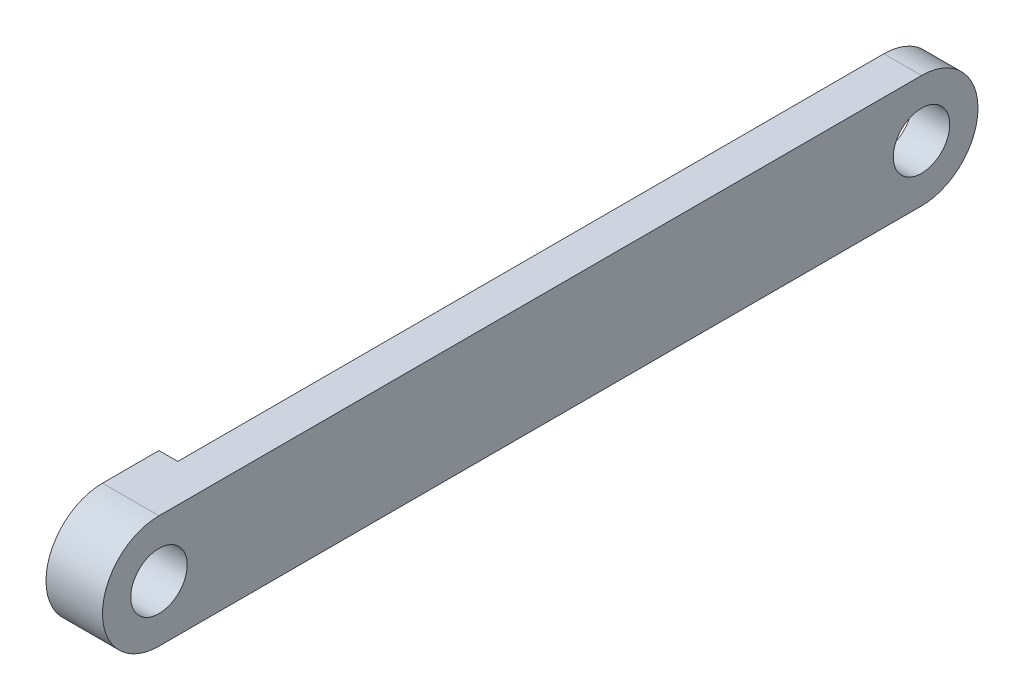
SolidWorks part; units mm, degrees
material "Plain Carbon Steel"
ref_plane "Front Plane" through (0, 0, 0) normal (0, 0, 1) x (1, 0, 0)
ref_plane "Top Plane" through (0, 0, 0) normal (0, 1, 0) x (1, 0, 0)
ref_plane "Right Plane" through (0, 0, 0) normal (1, 0, 0) x (0, 0, -1)
sketch "Sketch1" plane through (0, 0, 0) normal (1, 0, 0) x (0, 0, -1)
  line L24 (0, 3) -> (40.5, 3)
  line L25 (0, -3) -> (40.5, -3)
  arc A6 (0, 3) -> (0, -3) centre (0, 0) ccw
  arc A8 (40.5, 3) -> (40.5, -3) centre (40.5, 0) cw
  circle A10 centre (0, 0) radius 1.5
  circle A11 centre (40.5, 0) radius 1.5
  dimension "D1" = 6
  dimension "D2" = 40.5
  dimension "D3" = 3
extrude "Boss-Extrude1" add sketch "Sketch1" along normal blind 3
sketch "Sketch3" plane through (0, 0, 0) normal (-1, 0, 0) x (0, 0, 1)
  line L0 (-43.5, 3) -> (-3, 3)
  line L1 (-40.5, 3) -> (0, 3) construction
  line L2 (-3, 3) -> (-3, -3)
  line L3 (0, -3) -> (-40.5, -3) construction
  line L4 (-3, -3) -> (-43.5, -3)
  line L5 (-43.5, -3) -> (-43.5, 3)
  arc A0 (0, -3) -> (0, 3) centre (0, 0) ccw construction
  arc A1 (-40.5, 3) -> (-40.5, -3) centre (-40.5, 0) ccw construction
  dimension "D1" = 3
extrude "Cut-Extrude2" cut sketch "Sketch3" against normal blind 1
